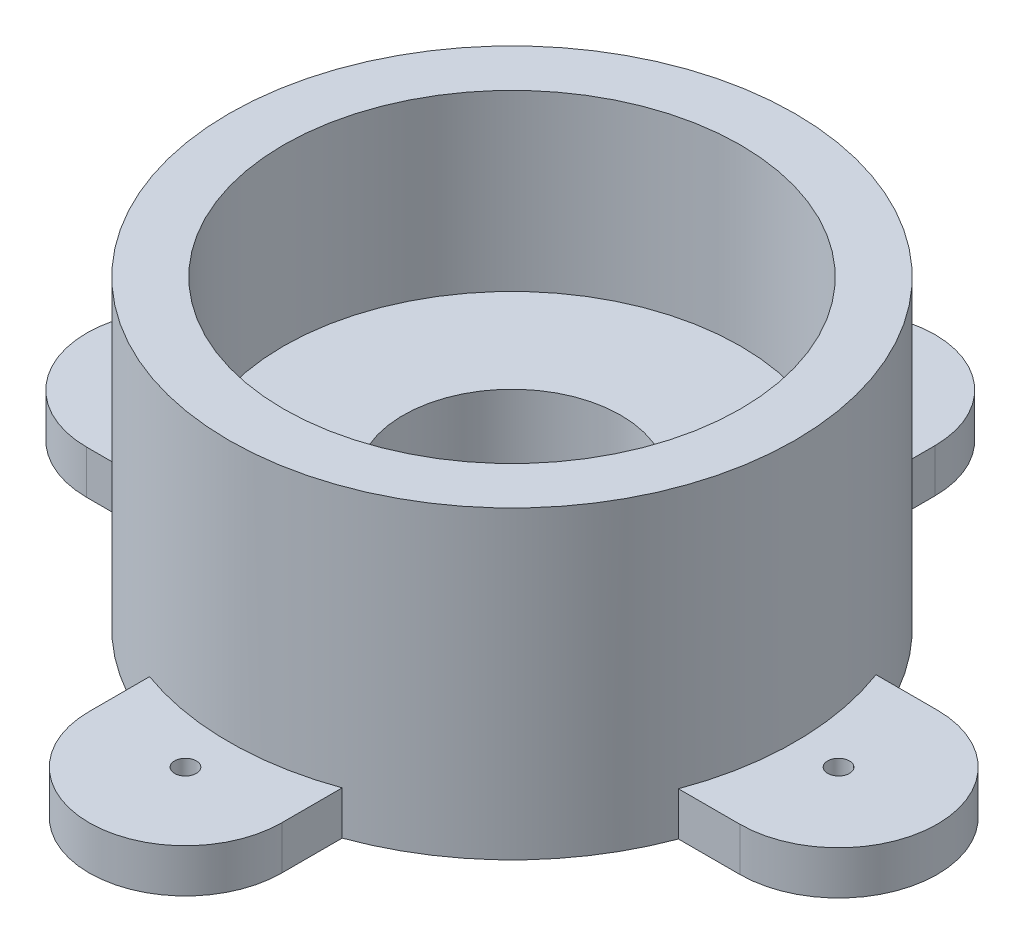
SolidWorks part; units mm, degrees
ref_plane "Front Plane" through (0, 0, 0) normal (0, 0, 1) x (1, 0, 0)
ref_plane "Top Plane" through (0, 0, 0) normal (0, 1, 0) x (1, 0, 0)
ref_plane "Right Plane" through (0, 0, 0) normal (1, 0, 0) x (0, 0, -1)
sketch "Sketch1" plane through (0, 0, 0) normal (1, 0, 0) x (0, 0, -1)
  line L0 (0, 0) -> (25, 0) construction
  line L1 (25, 0) -> (25, -20)
  line L2 (25, 0) -> (52.5, 0)
  line L3 (52.5, 0) -> (52.5, 40)
  line L4 (52.5, 40) -> (65, 40)
  line L5 (65, 40) -> (65, -20)
  line L6 (65, -20) -> (25, -20) construction
  line L7 (0, 0) -> (0, 10) construction
  line L8 (25, -20) -> (0, -20)
  line L9 (0, -20) -> (0, -30)
  line L10 (0, -30) -> (65, -30)
  line L11 (65, -30) -> (65, -20)
  dimension "D1" = 25
  dimension "D2" = 10
  dimension "D3" = 52.5
  dimension "D4" = 40
  dimension "D5" = 20
  dimension "D6" = 40
  dimension "D7" = 10
revolve "Revolve1" add sketch "Sketch1" angle 360 about L7
sketch "Sketch2" plane through (0, 0, 0) normal (0, 1, 0) x (1, 0, 0)
  line L0 (-75, 0) -> (75, 0) construction
  line L1 (-75, 22.6878) -> (75, 22.6878)
  line L2 (-75, -22.6878) -> (75, -22.6878)
  line L3 (0, 75) -> (0, -75) construction
  line L4 (22.1192, 75) -> (22.1192, -75)
  line L5 (-22.1192, 75) -> (-22.1192, -75)
  arc A0 (-75, 22.6878) -> (-75, -22.6878) centre (-75, 0) ccw
  arc A1 (75, -22.6878) -> (75, 22.6878) centre (75, 0) ccw
  arc A2 (22.1192, 75) -> (-22.1192, 75) centre (0, 75) ccw
  arc A3 (-22.1192, -75) -> (22.1192, -75) centre (0, -75) ccw
  circle A4 centre (0, 75) radius 2.5
  circle A5 centre (75, 0) radius 2.5
  circle A6 centre (0, -75) radius 2.5
  circle A7 centre (-75, 0) radius 2.5
  point P3 (0, 0)
  point P8 (0, 0)
  point P23 (-79.1071, 0)
  dimension "D1" = 5
  dimension "D2" = 150
  dimension "D3" = 150
extrude "Boss-Extrude1" add sketch "Sketch2" along normal blind 10 from surface contours L1 A0 L2 L5 A7 | L1 L5 L2 L4 | L4 A2 L5 L1 A4 | L2 A1 L1 L4 A5 | L5 A3 L4 L2 A6 region at (-57.5436, 0, 0) region at (0, 0, -57.5941) region at (0, 0, 0) region at (57.5436, 0, 0) region at (0, 0, 57.5941) starting at face at (0, -30, -65)
